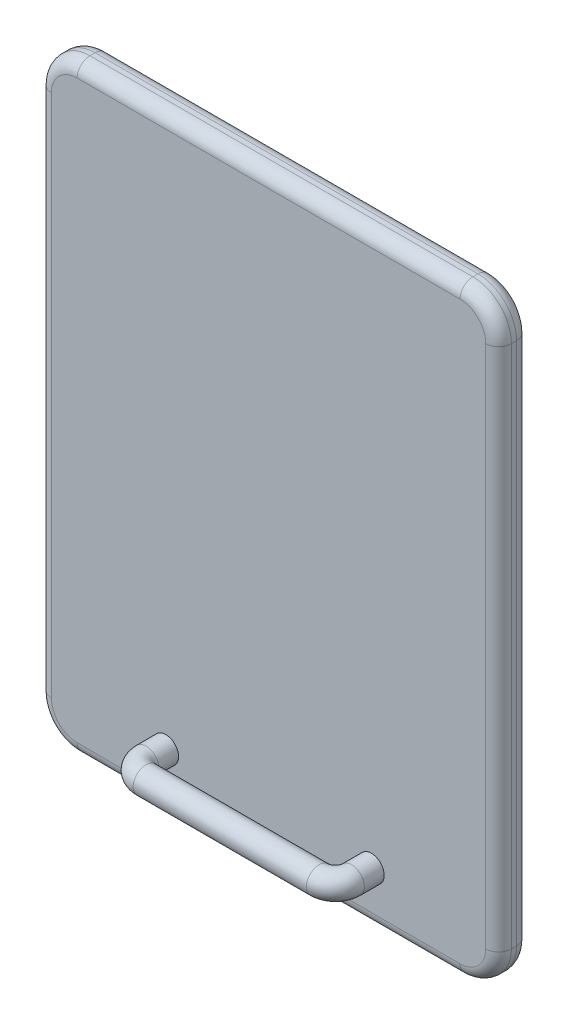
SolidWorks part; units mm, degrees
material "ABS PC"
ref_plane "Front Plane" through (0, 0, 0) normal (0, 0, 1) x (1, 0, 0)
ref_plane "Top Plane" through (0, 0, 0) normal (0, 1, 0) x (1, 0, 0)
ref_plane "Right Plane" through (0, 0, 0) normal (1, 0, 0) x (0, 0, -1)
sketch "Block sketch 1" plane through (0, 0, 0) normal (0, 0, 1) x (1, 0, 0)
  line L0 (683, -117) -> (832, -117)
  line L1 (847, -102) -> (847, 102)
  line L2 (832, 117) -> (683, 117)
  line L3 (668, 102) -> (668, -102)
  arc A0 (832, -117) -> (847, -102) centre (832, -102) ccw
  arc A1 (847, 102) -> (832, 117) centre (832, 102) ccw
  arc A2 (683, 117) -> (668, 102) centre (683, 102) ccw
  arc A3 (668, -102) -> (683, -117) centre (683, -102) ccw
  dimension "D1" = 15
  dimension "D2" = 179
  dimension "D3" = 234
extrude "Block 1" add sketch "Block sketch 1" along normal blind 12 from offset 543 separate body
fillet "Block edge fillet 1" radius 5 16 edges at (672.3934, -112.6066, 555) (672.3934, 112.6066, 555) (842.6066, 112.6066, 555) (842.6066, -112.6066, 555) (842.6066, 112.6066, 543) (842.6066, -112.6066, 543) (757.5, -117, 543) (672.3934, -112.6066, 543) (668, 0, 543) (672.3934, 112.6066, 543) (847, 0, 555) (668, 0, 555) (757.5, 117, 555) (757.5, -117, 555) (847, 0, 543) (757.5, 117, 543)
sketch3d "Pipe path 1"
  line L0 (717.5, -97, 555) -> (717.5, -97, 562.7)
  line L1 (723.8, -97, 569) -> (791.2, -97, 569)
  line L2 (797.5, -97, 562.7) -> (797.5, -97, 555)
  arc A0 (717.5, -97, 562.7) -> (723.8, -97, 569) centre (723.8, -97, 562.7) ccw
  arc A1 (791.2, -97, 569) -> (797.5, -97, 562.7) centre (791.2, -97, 562.7) ccw
  point P6 (717.5, -97, 569)
  point P7 (723.8, -90.7, 562.7)
  point P10 (797.5, -97, 569)
  point P11 (791.2, -90.7, 562.7)
  dimension "D1" = 6.3
  dimension "D2" = 6.3
sweep "Pipe 1" add path "Pipe path 1" circular profile diameter 10 parameters "D3"=10
combine bodies "Combine (weld / assembly of features)" operation type add bodies to combine 102 101
